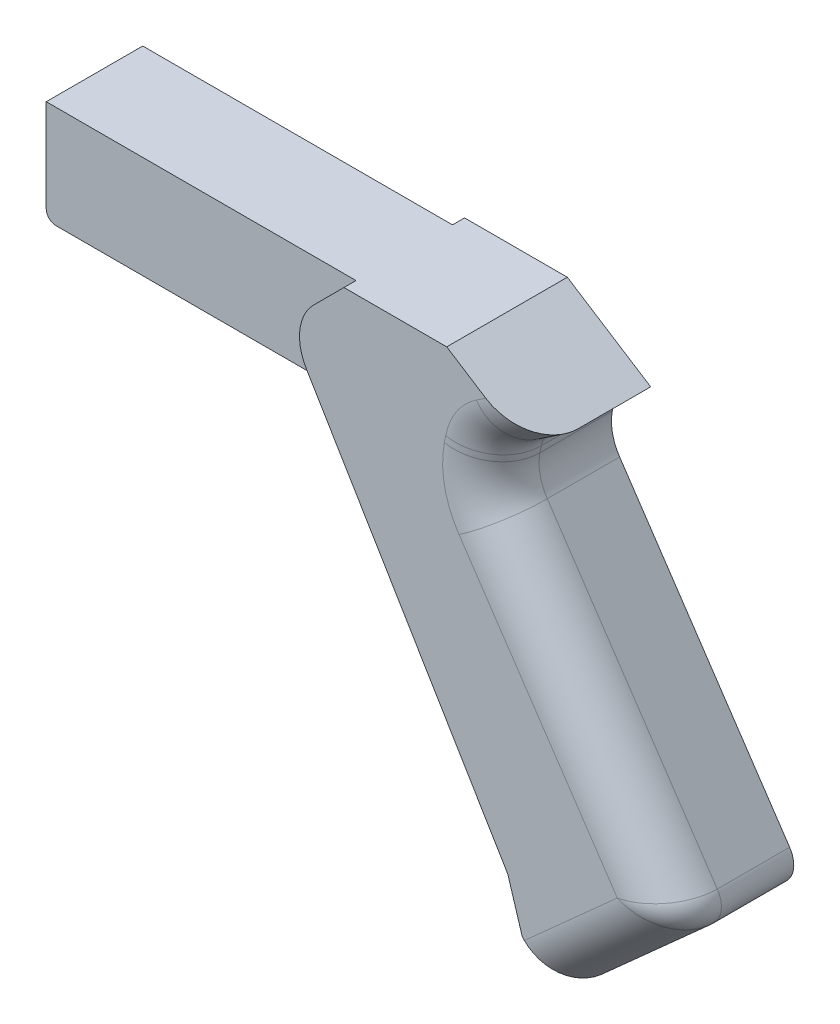
SolidWorks part; units mm, degrees
ref_plane "Front Plane" through (0, 0, 0) normal (0, 0, 1) x (1, 0, 0)
ref_plane "Top Plane" through (0, 0, 0) normal (0, 1, 0) x (1, 0, 0)
ref_plane "Right Plane" through (0, 0, 0) normal (1, 0, 0) x (0, 0, -1)
sketch "Sketch1" plane through (0, 0, 0) normal (0, 0, 1) x (1, 0, 0)
  line L0 (534.156, 163.2394) -> (534.156, 138.7949)
  line L1 (474.5094, 163.2394) -> (642.7743, 163.2394) construction
  line L2 (536.696, 136.2549) -> (640.0342, 136.2549)
  line L3 (640.0342, 136.2549) -> (642.7743, 163.2394)
  line L4 (642.7743, 163.2394) -> (534.156, 163.2394)
  arc A0 (534.156, 138.7949) -> (536.696, 136.2549) centre (536.696, 138.7949) ccw
  dimension "D1" = 2.54
extrude "Boss-Extrude1" add sketch "Sketch1" along normal blind 12.7 and the other way blind 12.7 contours L2 L3 L4 L0 A0
sketch "Sketch2" plane through (0, 0, 0) normal (0, 0, 1) x (1, 0, 0)
  line L0 (615.7164, 163.2394) -> (607.7319, 155.2549)
  line L1 (474.5094, 163.2394) -> (642.7743, 163.2394) construction
  line L2 (605.812, 139.7573) -> (658.8604, 51.0338)
  line L3 (658.8604, 51.0338) -> (662.6742, 38.6389)
  line L4 (662.6742, 38.6389) -> (672.2088, 29.1043)
  line L5 (672.2088, 29.1043) -> (700.2754, 54.2603)
  line L6 (701.3078, 62.5304) -> (656.545, 129.1492)
  line L7 (654.621, 138.662) -> (654.9629, 140.4162)
  line L8 (657.6541, 144.472) -> (664.7199, 149.2196)
  line L9 (642.7743, 163.2394) -> (668.5905, 146.7469) construction
  line L10 (664.7199, 149.2196) -> (642.7743, 163.2394)
  line L11 (642.7743, 163.2394) -> (615.7164, 163.2394)
  arc A0 (607.7319, 155.2549) -> (605.812, 139.7573) centre (616.7122, 146.2746) ccw
  arc A1 (656.545, 129.1492) -> (654.621, 138.662) centre (667.0864, 136.2322) cw
  arc A2 (654.9629, 140.4162) -> (657.6541, 144.472) centre (661.1956, 139.2013) cw
  arc A3 (700.2754, 54.2603) -> (701.3078, 62.5304) centre (696.0371, 58.9889) ccw
  dimension "D1" = 12.7
  dimension "D2" = 12.7
  dimension "D3" = 6.35
  dimension "D4" = 6.35
extrude "Boss-Extrude2" add sketch "Sketch2" along normal blind 15.875 and the other way blind 15.875
fillet "Fillet1" radius 12.7 7 edges at (686.2421, 41.6823, 15.875) (702.3382, 58.2023, 15.875) (661.187, 146.8458, 15.875) (655.9045, 142.7122, 15.875) (654.792, 139.5391, 15.875) (654.6385, 133.7146, 15.875) (678.9264, 95.8398, 15.875)
